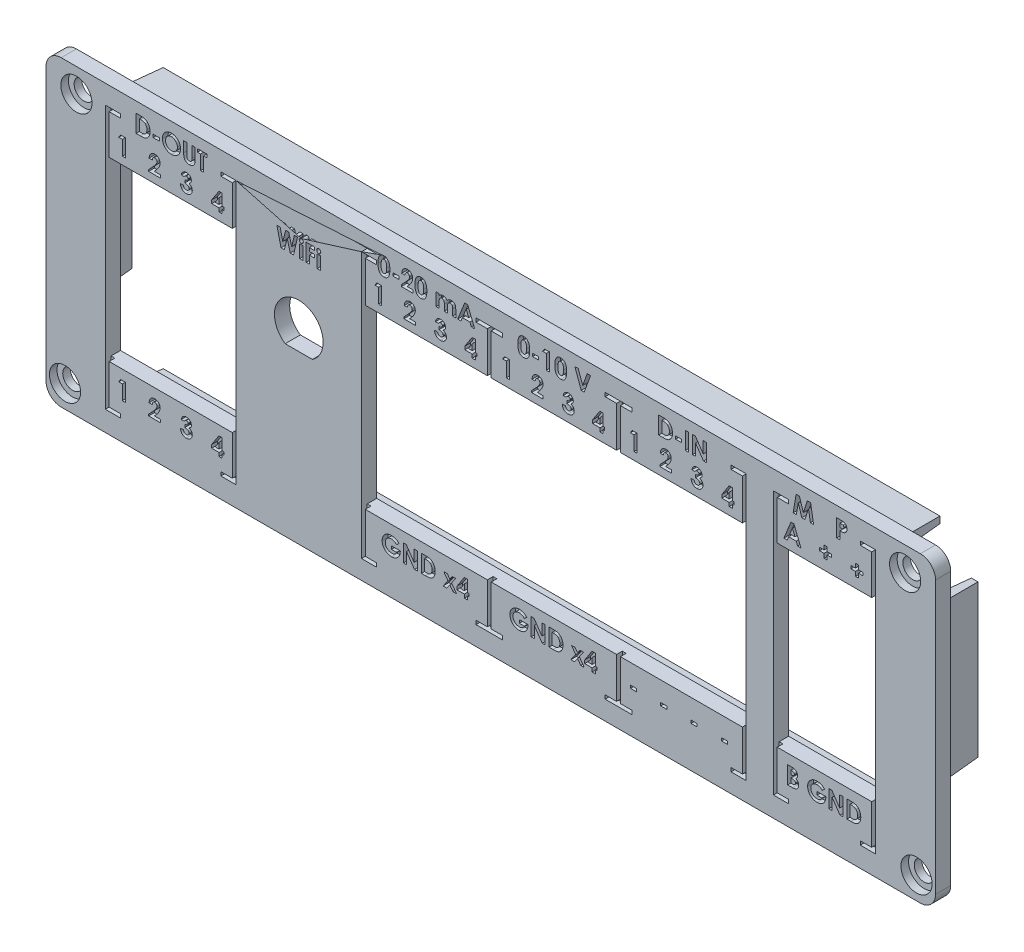
SolidWorks part; units mm, degrees
other "Markup1"
sketch "Sketch25" plane through (-58.5, 2, 19.9) normal (-0.4493, 0.8869, 0.1077) x (-0.8892, -0.4555, 0.042)
ref_plane "Front Plane" through (0, 0, 0) normal (0, 0, 1) x (1, 0, 0)
ref_plane "Top Plane" through (0, 0, 0) normal (0, 1, 0) x (1, 0, 0)
ref_plane "Right Plane" through (0, 0, 0) normal (1, 0, 0) x (0, 0, -1)
sketch "Sketch1" plane through (0, 0, 0) normal (0, 0, 1) x (1, 0, 0)
  line L0 (-58.5, -17.8) -> (-58.5, 18)
  line L1 (56.5, -17.9) -> (-56.5, -17.9) construction
  line L2 (56.5, -17.9) -> (56.5, 17.9) construction
  line L3 (56.5, 17.9) -> (-56.5, 17.9) construction
  line L4 (-56.5, -17.9) -> (-56.5, 17.9) construction
  line L5 (0, 17.9) -> (0, -17.9) construction
  line L6 (56.5, 0) -> (-56.5, 0) construction
  line L7 (58.5, -17.8) -> (58.5, 18)
  line L8 (56.5, 20) -> (-56.5, 20)
  line L9 (56.5, -19.8) -> (-56.5, -19.8)
  arc A0 (56.5, -19.8) -> (58.5, -17.8) centre (56.5, -17.8) ccw
  arc A1 (-56.5, -19.8) -> (-58.5, -17.8) centre (-56.5, -17.8) cw
  arc A2 (-56.5, 20) -> (-58.5, 18) centre (-56.5, 18) ccw
  arc A3 (58.5, 18) -> (56.5, 20) centre (56.5, 18) ccw
  circle A7 centre (-54.5, 16.85) radius 1.3
  circle A8 centre (-56, -16.85) radius 1.3
  circle A9 centre (56, -16.85) radius 1.3
  circle A10 centre (54.5, 16.85) radius 1.3
  point P0 (0, 0)
  dimension "D8" = 16.85
  dimension "D1" = 35.8
  dimension "D2" = 113
  dimension "D6" = 2
  dimension "D7" = 16.85
  dimension "D9" = 54.5
  dimension "D10" = 56
  dimension "D3" = 1.9
  dimension "D4" = 2.1
  dimension "D5" = 2
extrude "Boss-Extrude1" add sketch "Sketch1" along normal blind 2
sketch "Sketch3" plane through (0, 0, 0) normal (0, 0, -1) x (1, 0, 0)
  line L4 (0, 0) -> (-65.5905, 0) construction
  line L5 (51.4, -17.9) -> (-51.4, -17.9)
  line L6 (51.4, -17.9) -> (51.4, -16.4)
  line L7 (51.4, -16.4) -> (-51.4, -16.4)
  line L8 (-56.4, 17.7) -> (-56.4, -17.9)
  line L9 (-56.4, -17.9) -> (56.4, -17.9)
  line L10 (56.4, -17.9) -> (56.4, 17.7)
  line L11 (56.4, 17.7) -> (-56.4, 17.7)
  line L12 (-56.4, 17.7) -> (-56.4, -17.9) construction
  line L13 (-56.4, -17.9) -> (56.4, -17.9) construction
  line L14 (56.4, -17.9) -> (56.4, 17.7) construction
  line L15 (56.4, 17.7) -> (-56.4, 17.7) construction
  line L16 (-51.4, -17.9) -> (-51.4, -16.4)
  line L17 (-51.4, 17.9) -> (-51.4, 16.4)
  line L18 (51.4, 16.4) -> (-51.4, 16.4)
  line L19 (51.4, 17.9) -> (51.4, 16.4)
  line L20 (51.4, 17.9) -> (-51.4, 17.9)
  line L21 (0, 0) -> (0, 10.6719) construction
  line L22 (56.4, -12.9) -> (54.9, -12.9)
  line L23 (56.4, -12.9) -> (56.4, 7.7)
  line L24 (56.4, 7.7) -> (54.9, 7.7)
  line L25 (54.9, -12.9) -> (54.9, 7.7)
  line L26 (-54.9, -12.9) -> (-54.9, 7.7)
  line L27 (-56.4, 7.7) -> (-54.9, 7.7)
  line L28 (-56.4, -12.9) -> (-56.4, 7.7)
  line L29 (-56.4, -12.9) -> (-54.9, -12.9)
  point P4 (51.4, -17.15)
  dimension "D2" = 5
  dimension "D3" = 5
  dimension "D4" = 1.5
  dimension "D5" = 1.5
  dimension "D6" = 10
  dimension "D7" = 5
  dimension "D1" = 2.1
extrude "Boss-Extrude2" add sketch "Sketch3" along normal blind 6 draft 3
sketch "Sketch6" plane through (0, 0, 2) normal (0, 0, 1) x (1, 0, 0)
  circle A15 centre (56, -16.85) radius 2.05
  circle A16 centre (56, -16.85) radius 2.05
  circle A18 centre (54.5, 16.85) radius 2.05
  circle A19 centre (54.5, 16.85) radius 2.05
  circle A21 centre (-54.5, 16.85) radius 2.05
  circle A22 centre (-54.5, 16.85) radius 2.05
  circle A24 centre (-56, -16.85) radius 2.05
  circle A25 centre (-56, -16.85) radius 2.05
  dimension "D1" = 0.75
  dimension "D2" = 0.75
  dimension "D3" = 0.75
  dimension "D4" = 0.75
extrude "Cut-Extrude3" cut sketch "Sketch6" against normal blind 1
sketch "Sketch5" plane through (0, 0, 0) normal (0, 0, -1) x (1, 0, 0)
  line L1 (-57.5, 10.95) -> (57.5, 10.95) construction
  line L2 (-57.5, 10.95) -> (-57.5, 12.55) construction
  line L3 (-57.5, 12.55) -> (57.5, 12.55) construction
  line L12 (57.5, 10.95) -> (57.5, 12.55) construction
  line L13 (0, 12.55) -> (0, 10.95) construction
  line L14 (-57.5, 11.75) -> (57.5, 11.75) construction
  line L17 (-56.5, 19.8) -> (56.5, 19.8) construction
  point P0 (0, 11.75)
  dimension "D1" = 115
  dimension "D2" = 1.6
  dimension "D3" = 7.25
sketch "Sketch30" plane through (0, 0, 2) normal (0, 0, 1) x (1, 0, 0)
  line L1 (50.6, 11.8) -> (37.18, 11.8)
  line L2 (50.6, 11.8) -> (50.6, -11.45)
  line L3 (50.6, -11.45) -> (37.18, -11.45)
  line L4 (37.18, 11.8) -> (37.18, -11.45)
  line L5 (-57.5, -10.95) -> (57.5, -10.95) construction
  line L6 (-17, 4.8) -> (-33.5, 4.8) construction
  line L7 (-17, -11.45) -> (33.6, -11.45)
  line L8 (-17, -11.45) -> (-17, 11.8)
  line L9 (-17, 11.8) -> (33.6, 11.8)
  line L10 (33.6, -11.45) -> (33.6, 11.8)
  line L11 (-50.7, -11.45) -> (-33.5, -11.45)
  line L12 (-50.7, -11.45) -> (-50.7, 11.8)
  line L13 (-50.7, 11.8) -> (-33.5, 11.8)
  line L14 (-33.5, -11.45) -> (-33.5, 11.8)
  line L15 (-27.0437, 2.15) -> (-23.4563, 2.15)
  line L16 (57.5, -10.95) -> (57.5, -12.55) construction
  circle A0 centre (-25.25, 4.8) radius 3.2 construction
  arc A1 (-27.0437, 2.15) -> (-23.4563, 2.15) centre (-25.25, 4.8) cw
  point P22 (-25.25, 8)
  dimension "D10" = 6.4
  dimension "D2" = 13.42
  dimension "D3" = 23.25
  dimension "D4" = 0.5
  dimension "D5" = 74.5
  dimension "D6" = 50.6
  dimension "D7" = 91
  dimension "D8" = 17.2
  dimension "D9" = 7
  dimension "D11" = 5.85
  dimension "D12" = 6.9
extrude "Cut-Extrude19" cut sketch "Sketch30" against normal up to surface (2 mm away) up to face at (-57.3, -16.85, 0)
sketch "Sketch31" plane through (0, 0, 2) normal (0, 0, 1) x (1, 0, 0)
  line L0 (-33.5, 16.3) -> (-50.7, 16.3) construction
  line L1 (33.6, -11.45) -> (33.6, 11.8) construction
  line L2 (-50.7, 11.8) -> (-50.7, -11.45) construction
  line L3 (-17, 11.8) -> (-17, -11.45) construction
  line L4 (37.18, -15.0589) -> (50.6, -15.0589) construction
  line L5 (1.3, -15.0589) -> (15.1, -15.0589) construction
  line L6 (-33.5, -11.45) -> (-33.5, 11.8) construction
  line L7 (-49.2, 12.8) -> (-35, 12.8) construction
  line L8 (-33.5, 11.8) -> (-50.7, 11.8) construction
  line L9 (-15.5, -15.0589) -> (-1.7, -15.0589) construction
  line L10 (-0.2, 3.2212) -> (-0.2, 10.2378) construction
  line L11 (16.6, 3.2212) -> (16.6, 10.2378) construction
  line L12 (18.1, -15.0589) -> (32.1, -15.0589) construction
  line L13 (38.5113, 12.8) -> (49.2325, 12.8) construction
  line L14 (37.18, 16.3) -> (50.6, 16.3) construction
  line L15 (37.18, 11.8) -> (37.18, -11.45) construction
  line L16 (50.6, -11.45) -> (50.6, 11.8) construction
  line L17 (-33.5, 12.8) -> (-17, 12.8) construction
  line L18 (33.6, 11.8) -> (-17, 11.8) construction
  line L19 (-15.5, 12.8) -> (-1.7, 12.8) construction
  line L20 (1.3, 12.8) -> (15.1, 12.8) construction
  line L21 (18.1, 12.8) -> (32.1, 12.8) construction
  line L23 (-17, 16.3) -> (-0.2, 16.3) construction
  line L24 (-0.2, 16.3) -> (16.6, 16.3) construction
  line L25 (16.6, 16.3) -> (33.6, 16.3) construction
  line L26 (-49.2, -15.0589) -> (-35, -15.0589) construction
  line L27 (-17, 11.8) -> (-17, 17.65)
  line L28 (-17, 17.65) -> (-15, 17.65)
  line L29 (-15, 17.65) -> (-15, 17.15)
  line L30 (-15, 17.15) -> (-16.5, 17.15)
  line L31 (-16.5, 17.15) -> (-16.5, 11.8)
  line L32 (-16.5, 11.8) -> (-17, 11.8)
  line L33 (-1.95, 17.65) -> (1.55, 17.65)
  line L34 (1.55, 17.65) -> (1.55, 17.15)
  line L35 (1.55, 17.15) -> (0.05, 17.15)
  line L36 (0.05, 17.15) -> (0.05, 11.8)
  line L37 (0.05, 11.8) -> (-0.45, 11.8)
  line L38 (-0.45, 11.8) -> (-0.45, 17.15)
  line L39 (-0.45, 17.15) -> (-1.95, 17.15)
  line L40 (-1.95, 17.15) -> (-1.95, 17.65)
  line L41 (-0.45, 13.1625) -> (0.05, 13.1625) construction
  line L42 (-1.95, 17.15) -> (1.55, 17.65) construction
  line L43 (-17, 11.8) -> (33.6, -11.45) construction
  line L44 (8.3, 0.175) -> (8.3, 8.2587) construction
  line L45 (33.1, 11.8) -> (33.6, 11.8)
  line L46 (33.1, 17.15) -> (33.1, 11.8)
  line L47 (31.6, 17.15) -> (33.1, 17.15)
  line L48 (31.6, 17.65) -> (31.6, 17.15)
  line L49 (33.6, 17.65) -> (31.6, 17.65)
  line L50 (33.6, 11.8) -> (33.6, 17.65)
  line L51 (18.55, 17.15) -> (15.05, 17.65) construction
  line L52 (17.05, 13.1625) -> (16.55, 13.1625) construction
  line L53 (18.55, 17.15) -> (18.55, 17.65)
  line L54 (17.05, 17.15) -> (18.55, 17.15)
  line L55 (17.05, 11.8) -> (17.05, 17.15)
  line L56 (16.55, 11.8) -> (17.05, 11.8)
  line L57 (16.55, 17.15) -> (16.55, 11.8)
  line L58 (15.05, 17.15) -> (16.55, 17.15)
  line L59 (15.05, 17.65) -> (15.05, 17.15)
  line L60 (18.55, 17.65) -> (15.05, 17.65)
  line L61 (-50.7, 11.8) -> (-50.7, 17.5)
  line L62 (-50.7, 17.5) -> (-48.7, 17.5)
  line L63 (-48.7, 17.5) -> (-48.7, 17)
  line L64 (-48.7, 17) -> (-50.2, 17)
  line L65 (-50.2, 17) -> (-50.2, 11.8)
  line L66 (-50.2, 11.8) -> (-50.7, 11.8)
  line L67 (-50.7, 0.175) -> (-33.5, 0.175) construction
  line L68 (-42.1, 0.175) -> (-42.1, 6.3415) construction
  line L69 (-34, 11.8) -> (-33.5, 11.8)
  line L70 (-34, 17) -> (-34, 11.8)
  line L71 (-35.5, 17) -> (-34, 17)
  line L72 (-35.5, 17.5) -> (-35.5, 17)
  line L73 (-33.5, 17.5) -> (-35.5, 17.5)
  line L74 (-33.5, 11.8) -> (-33.5, 17.5)
  line L75 (-33.5, -11.45) -> (-33.5, -17.15)
  line L76 (-33.5, -17.15) -> (-35.5, -17.15)
  line L77 (-35.5, -17.15) -> (-35.5, -16.65)
  line L78 (-35.5, -16.65) -> (-34, -16.65)
  line L79 (-34, -16.65) -> (-34, -11.45)
  line L80 (-34, -11.45) -> (-33.5, -11.45)
  line L81 (-50.2, -11.45) -> (-50.7, -11.45)
  line L82 (-50.2, -16.65) -> (-50.2, -11.45)
  line L83 (-48.7, -16.65) -> (-50.2, -16.65)
  line L84 (-48.7, -17.15) -> (-48.7, -16.65)
  line L85 (-50.7, -17.15) -> (-48.7, -17.15)
  line L86 (-50.7, -11.45) -> (-50.7, -17.15)
  line L87 (-17, 0.175) -> (33.6, 0.175) construction
  line L88 (33.6, -11.45) -> (33.6, -17.3)
  line L89 (33.6, -17.3) -> (31.6, -17.3)
  line L90 (31.6, -17.3) -> (31.6, -16.8)
  line L91 (31.6, -16.8) -> (33.1, -16.8)
  line L92 (33.1, -16.8) -> (33.1, -11.45)
  line L93 (33.1, -11.45) -> (33.6, -11.45)
  line L94 (17.05, -12.8125) -> (16.55, -12.8125) construction
  line L95 (18.55, -16.8) -> (15.05, -17.3) construction
  line L96 (18.55, -17.3) -> (15.05, -17.3)
  line L97 (15.05, -17.3) -> (15.05, -16.8)
  line L98 (15.05, -16.8) -> (16.55, -16.8)
  line L99 (16.55, -16.8) -> (16.55, -11.45)
  line L100 (16.55, -11.45) -> (17.05, -11.45)
  line L101 (17.05, -11.45) -> (17.05, -16.8)
  line L102 (17.05, -16.8) -> (18.55, -16.8)
  line L103 (18.55, -16.8) -> (18.55, -17.3)
  line L104 (-1.95, -16.8) -> (1.55, -17.3) construction
  line L105 (-0.45, -12.8125) -> (0.05, -12.8125) construction
  line L106 (-1.95, -16.8) -> (-1.95, -17.3)
  line L107 (-0.45, -16.8) -> (-1.95, -16.8)
  line L108 (-0.45, -11.45) -> (-0.45, -16.8)
  line L109 (0.05, -11.45) -> (-0.45, -11.45)
  line L110 (0.05, -16.8) -> (0.05, -11.45)
  line L111 (1.55, -16.8) -> (0.05, -16.8)
  line L112 (1.55, -17.3) -> (1.55, -16.8)
  line L113 (-1.95, -17.3) -> (1.55, -17.3)
  line L114 (-16.5, -11.45) -> (-17, -11.45)
  line L115 (-16.5, -16.8) -> (-16.5, -11.45)
  line L116 (-15, -16.8) -> (-16.5, -16.8)
  line L117 (-15, -17.3) -> (-15, -16.8)
  line L118 (-17, -17.3) -> (-15, -17.3)
  line L119 (-17, -11.45) -> (-17, -17.3)
  line L120 (37.18, 11.8) -> (37.18, 17.5)
  line L121 (37.18, 17.5) -> (39.18, 17.5)
  line L122 (39.18, 17.5) -> (39.18, 17)
  line L123 (39.18, 17) -> (37.68, 17)
  line L124 (37.68, 17) -> (37.68, 11.8)
  line L125 (50.6, 11.8) -> (37.18, 11.8) construction
  line L126 (37.68, 11.8) -> (37.18, 11.8)
  line L127 (37.18, 0.175) -> (50.6, 0.175) construction
  line L128 (43.89, 0.175) -> (43.89, 6.3415) construction
  line L129 (50.1, 11.8) -> (50.6, 11.8)
  line L130 (50.1, 17) -> (50.1, 11.8)
  line L131 (48.6, 17) -> (50.1, 17)
  line L132 (48.6, 17.5) -> (48.6, 17)
  line L133 (50.6, 17.5) -> (48.6, 17.5)
  line L134 (50.6, 11.8) -> (50.6, 17.5)
  line L135 (50.6, -11.45) -> (50.6, -17.15)
  line L136 (50.6, -17.15) -> (48.6, -17.15)
  line L137 (48.6, -17.15) -> (48.6, -16.65)
  line L138 (48.6, -16.65) -> (50.1, -16.65)
  line L139 (50.1, -16.65) -> (50.1, -11.45)
  line L140 (50.1, -11.45) -> (50.6, -11.45)
  line L141 (37.68, -11.45) -> (37.18, -11.45)
  line L142 (37.68, -16.65) -> (37.68, -11.45)
  line L143 (39.18, -16.65) -> (37.68, -16.65)
  line L144 (39.18, -17.15) -> (39.18, -16.65)
  line L145 (37.18, -17.15) -> (39.18, -17.15)
  line L146 (37.18, -11.45) -> (37.18, -17.15)
  line L147 (38.5113, -15.0589) -> (49.2325, -15.0589) construction
  text T0 "<b>D-OUT</b>" font "Century Gothic" height 2.3
  text T1 "<b>1 2 3 4</b>" font "Century Gothic" height 2.3
  text T2 "<b>M   P </b>" font "Century Gothic" height 2.3
  text T3 "<b>A + +</b>" font "Century Gothic" height 2.3
  text T4 "<b>WiFi</b>" font "Century Gothic" height 2.3
  text T5 "<b>1 2 3 4</b>" font "Century Gothic" height 2.3
  text T6 "<b>1 2 3 4</b>" font "Century Gothic" height 2.3
  text T7 "<b>1 2 3 4</b>" font "Century Gothic" height 2.3
  text T8 "<b>D-IN</b>" font "Century Gothic" height 2.3
  text T9 "<b>0-20 mA</b>" font "Century Gothic" height 2.3
  text T10 "<b>0-10 V</b>" font "Century Gothic" height 2.3
  text T11 "<b>1 2 3 4</b>" font "Century Gothic" height 2.3
  text T12 "<b>GND x4</b>" font "Century Gothic" height 2.3
  text T13 "<b>GND x4</b>" font "Century Gothic" height 2.3
  text T14 "<b>- - - - </b>" font "Century Gothic" height 2.3
  text T15 "<b>B GND</b>" font "Century Gothic" height 2.3
  point P75 (-0.2, 13.1625)
  point P76 (-0.2, 17.4)
  point P169 (38.43, 17)
  dimension "D1" = 4.5
  dimension "D2" = 1
  dimension "D3" = 1.5
  dimension "D4" = 1.5
  dimension "D5" = 1
  dimension "D6" = 1.5
  dimension "D7" = 1.5
  dimension "D8" = 1.5
  dimension "D9" = 1.5
  dimension "D10" = 1.5
  dimension "D11" = 16.8
  dimension "D12" = 16.8
  dimension "D13" = 1.5
  dimension "D14" = 2
  dimension "D15" = 0.5
  dimension "D16" = 0.5
  dimension "D17" = 5.35
  dimension "D18" = 1.5
  dimension "D19" = 0.5
  dimension "D20" = 1.5
  dimension "D21" = 0.5
  dimension "D22" = 0.5
  dimension "D23" = 0.5
  dimension "D24" = 1.5
  dimension "D25" = 5.2
  dimension "D26" = 5.2
  dimension "D27" = 0.5
  dimension "D28" = 0.5
  dimension "D29" = 1.5
extrude "Cut-Extrude20" cut sketch "Sketch31" against normal blind 0.75
sketch "Sketch29" plane through (0, 0, 0) normal (0, 0, -1) x (1, 0, 0)
  line L0 (-25.2553, 15.2324) -> (-25.7553, 14.2324)
  line L1 (-25.7553, 14.2324) -> (-24.7553, 14.2324)
  line L2 (-24.7553, 14.2324) -> (-25.2553, 15.2324)
  line L3 (-26.2053, 16.1824) -> (-27.2053, 16.6824)
  line L4 (-27.2053, 16.6824) -> (-27.2053, 15.6824)
  line L5 (-27.2053, 15.6824) -> (-26.2053, 16.1824)
  line L6 (-25.2553, 17.1324) -> (-24.7553, 18.1324)
  line L7 (-24.7553, 18.1324) -> (-25.7553, 18.1324)
  line L8 (-25.7553, 18.1324) -> (-25.2553, 17.1324)
  line L9 (-24.3053, 16.1824) -> (-23.3053, 15.6824)
  line L10 (-23.3053, 15.6824) -> (-23.3053, 16.6824)
  line L11 (-23.3053, 16.6824) -> (-24.3053, 16.1824)
  circle A0 centre (-25.2553, 16.1824) radius 0.95 construction
  point P8 (-25.2553, 14.2324)
  point P21 (-25.2553, 16.1824)
  dimension "D1" = 1.9
  dimension "D2" = 1
  dimension "D3" = 1
  dimension "D4" = 4
